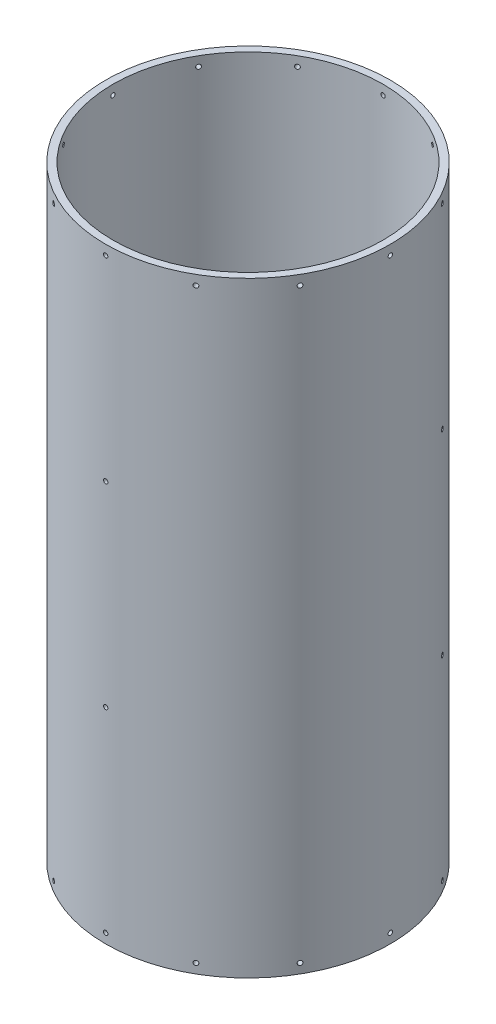
SolidWorks part; units mm, degrees
material "PVC Rigid"
ref_plane "Front Plane" through (0, 0, 0) normal (0, 0, 1) x (1, 0, 0)
ref_plane "Top Plane" through (0, 0, 0) normal (0, 1, 0) x (1, 0, 0)
ref_plane "Right Plane" through (0, 0, 0) normal (1, 0, 0) x (0, 0, -1)
sketch "Sketch1" plane through (0, 0, 0) normal (0, 1, 0) x (1, 0, 0)
  circle A0 centre (0, 0) radius 93.6625
  circle A1 centre (0, 0) radius 88.9
  dimension "D1" = 187.325
  dimension "D2" = 177.8
extrude "Boss-Extrude1" add sketch "Sketch1" along normal mid plane 398.78
ref_plane "Plane1" through (0, 0, 93.6625) normal (0, 0, 1) x (1, 0, 0)
sketch "Sketch3" plane through (0, 0, 93.6625) normal (0, 0, 1) x (1, 0, 0)
  line L0 (0, -55) -> (0, 55) construction
  line L1 (-93.6625, -199.39) -> (93.6625, -199.39) construction
  circle A0 centre (0, -193.04) radius 1.4351
  dimension "D1" = 2.8702
  dimension "D2" = 6.35
extrude "Cut-Extrude1" cut sketch "Sketch3" against normal blind 19.304
pattern_circular "CirPattern1" count 12 over 360 about axis through (0, 199.39, 0) along (0, -1, 0) of "Cut-Extrude1" reverse direction yes
mirror "Mirror1" about plane through (0, 0, 0) normal (0, 1, 0) of "CirPattern1", "Cut-Extrude1"
sketch "Sketch4" plane through (0, 0, 93.6625) normal (0, 0, 1) x (1, 0, 0)
  line L0 (0, -55) -> (0, 55) construction
  circle A0 centre (0, 64.3636) radius 1.4351
  circle A1 centre (0, -64.3636) radius 1.4351
  circle A2 centre (0, 193.04) radius 1.4351 construction
  circle A3 centre (0, -193.04) radius 1.4351 construction
  dimension "D1" = 128.6764
  dimension "D2" = 128.6764
  dimension "D3" = 2.8702
  dimension "D4" = 2.8702
extrude "Cut-Extrude2" cut sketch "Sketch4" against normal blind 43.18
pattern_circular "CirPattern2" count 3 over 360 about axis through (0, 199.39, 0) along (0, -1, 0) of "Cut-Extrude2"
